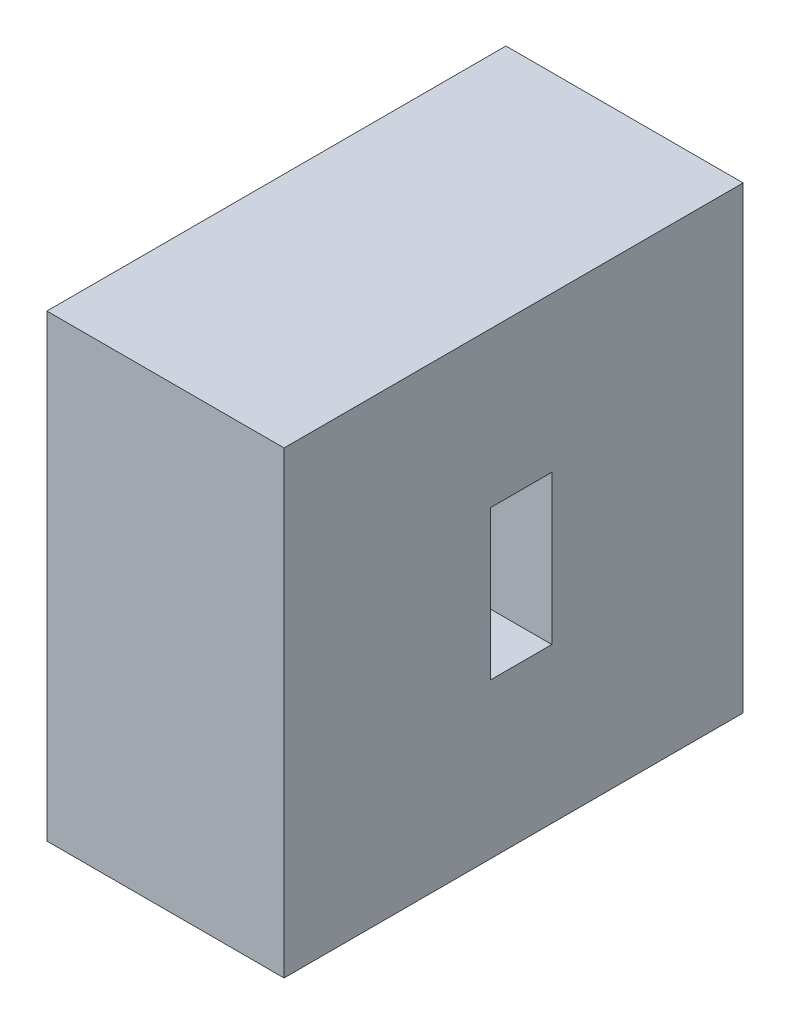
SolidWorks part; units mm, degrees
ref_plane "Front Plane" through (0, 0, 0) normal (0, 0, 1) x (1, 0, 0)
ref_plane "Top Plane" through (0, 0, 0) normal (0, 1, 0) x (1, 0, 0)
ref_plane "Right Plane" through (0, 0, 0) normal (1, 0, 0) x (0, 0, -1)
sketch "Sketch1" plane through (0, 0, 0) normal (0, 0, 1) x (1, 0, 0)
  line L1 (49.4, -6) -> (55.6, -6)
  line L2 (49.4, -6) -> (49.4, 6)
  line L3 (49.4, 6) -> (55.6, 6)
  line L4 (55.6, -6) -> (55.6, 6)
extrude "Boss-Extrude1" add sketch "Sketch1" along normal blind 12 from offset 144
sketch "Sketch2" plane through (0, 0, 0) normal (0, 0, 1) x (1, 0, 0)
  line L1 (52.9, -1.95) -> (55.7, -1.95)
  line L2 (52.9, -1.95) -> (52.9, 1.95)
  line L3 (52.9, 1.95) -> (55.7, 1.95)
  line L4 (55.7, -1.95) -> (55.7, 1.95)
extrude "Boss-Extrude2" add sketch "Sketch2" along normal blind 1.6 from offset 149 separate body
combine bodies "Combine1" operation type subtract main body 101 bodies to subtract 102
sketch "Sketch3" plane through (0, 0, 0) normal (0, 0, 1) x (1, 0, 0)
  line L1 (51.2, -1.95) -> (52.9, -1.95)
  line L2 (51.2, -1.95) -> (51.2, 1.95)
  line L3 (51.2, 1.95) -> (52.9, 1.95)
  line L4 (52.9, -1.95) -> (52.9, 1.95)
extrude "Boss-Extrude3" add sketch "Sketch3" along normal blind 2.1 from offset 149 separate body
combine bodies "Combine2" operation type subtract main body 103 bodies to subtract 104
